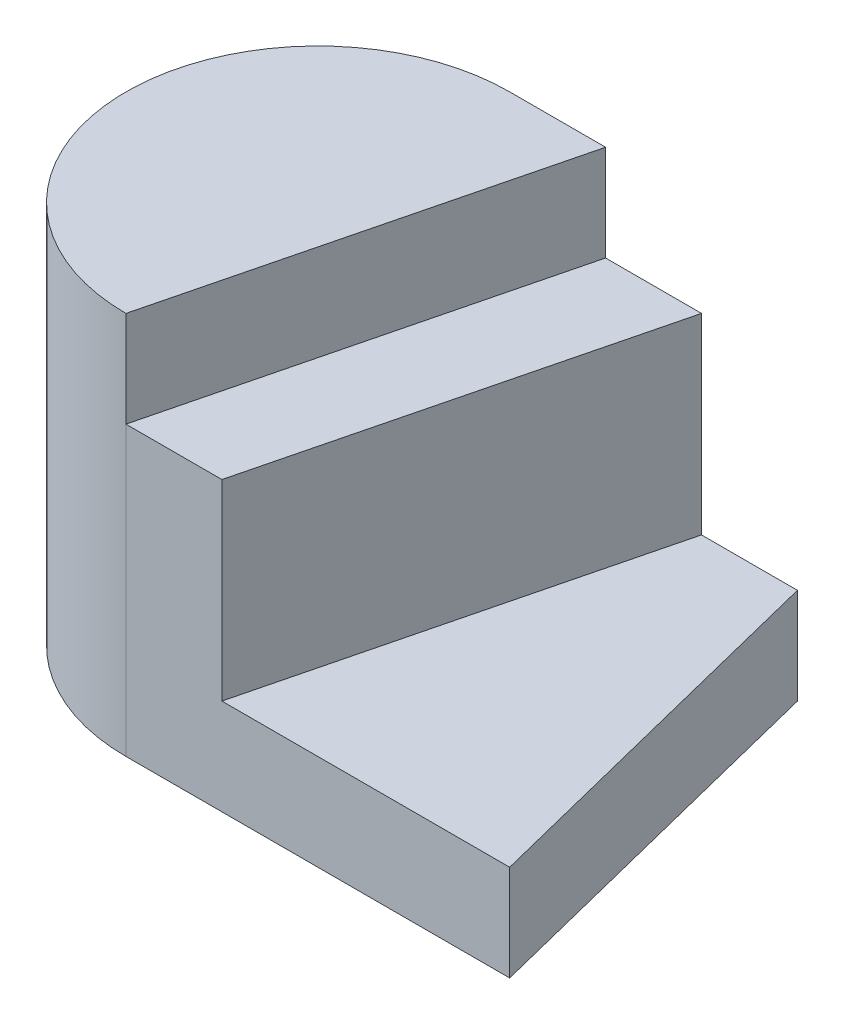
SolidWorks part; units mm, degrees
ref_plane "Front Plane" through (0, 0, 0) normal (0, 0, 1) x (1, 0, 0)
ref_plane "Top Plane" through (0, 0, 0) normal (0, 1, 0) x (1, 0, 0)
ref_plane "Right Plane" through (0, 0, 0) normal (1, 0, 0) x (0, 0, -1)
sketch "Sketch1" plane through (0, 0, 0) normal (0, 1, 0) x (1, 0, 0)
  line L0 (0, 508) -> (762, 508)
  line L1 (762, 508) -> (1016, -508)
  line L2 (1016, -508) -> (0, -508)
  line L3 (0, -508) -> (254, 508)
  line L4 (254, 669.6768) -> (254, 346.3232) construction
  line L5 (508, 508) -> (254, -508)
  line L6 (-508, 0) -> (-508, 1023.6626) construction
  line L7 (508, 669.6768) -> (508, 346.3232) construction
  arc A0 (0, 508) -> (0, -508) centre (0, 0) ccw
  point P5 (508, 486.0005)
  point P16 (0, 0)
  point P17 (254, 486.0005)
  point P18 (26.7874, -508)
  point P19 (508, -508)
  point P20 (508, -508)
  point P21 (254, -508)
  dimension "D1" = 1016
  dimension "D2" = 762
  dimension "D3" = 1524
  dimension "D4" = 254
  dimension "D5" = 254
extrude "Boss-Extrude1" add sketch "Sketch1" along normal blind 254 contours L0 L5 L2 L1 region at (635, 0, 84.6667)
extrude "Boss-Extrude2" add sketch "Sketch1<3>" along normal blind 762 contours L5 L0 L3 L2 region at (254, 0, 0)
sketch "Sketch1<3>" plane through (0, 0, 0) normal (0, 1, 0) x (1, 0, 0) same geometry as "Sketch1"
extrude "Boss-Extrude3" add sketch "Sketch1<4>" along normal blind 1016 contours L0 A0 L3 region at (-143.1011, 0, -40.886)
sketch "Sketch1<4>" plane through (0, 0, 0) normal (0, 1, 0) x (1, 0, 0) same geometry as "Sketch1"
